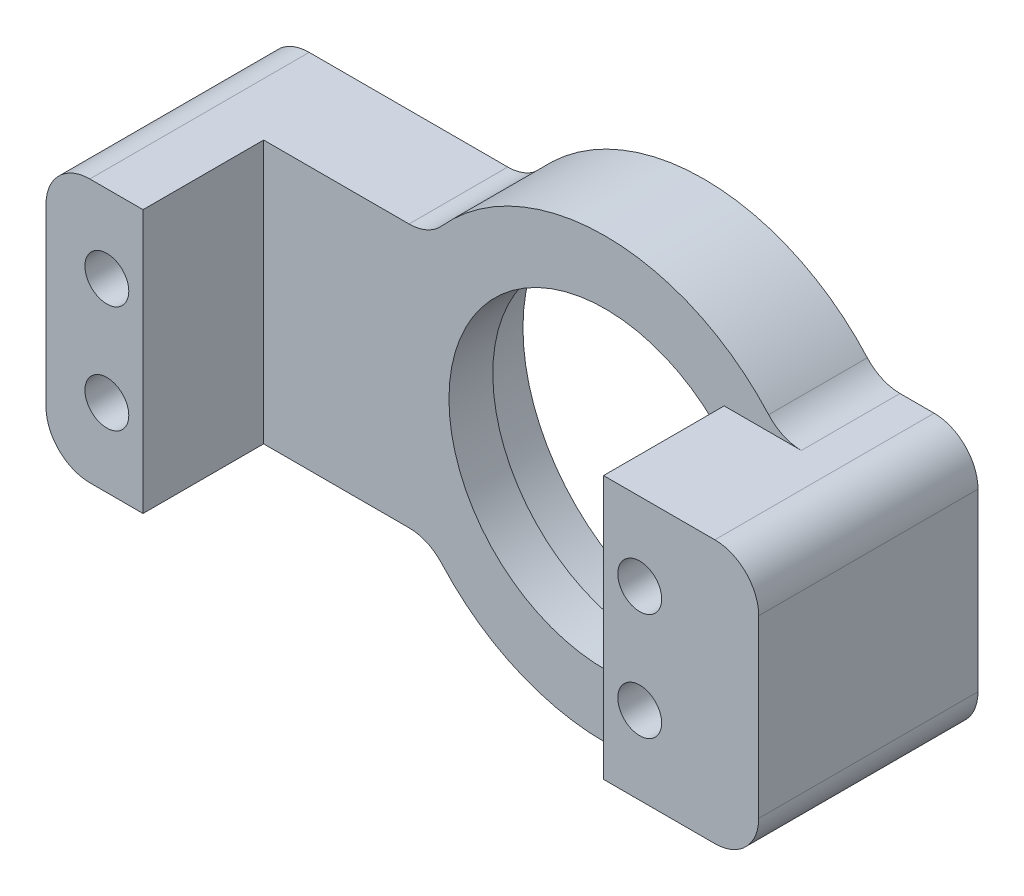
SolidWorks part; units mm, degrees
ref_plane "Front Plane" through (0, 0, 0) normal (0, 0, 1) x (1, 0, 0)
ref_plane "Top Plane" through (0, 0, 0) normal (0, 1, 0) x (1, 0, 0)
ref_plane "Right Plane" through (0, 0, 0) normal (1, 0, 0) x (0, 0, -1)
sketch "Sketch1" plane through (0, 0, 0) normal (0, 0, 1) x (1, 0, 0)
  line L0 (0, 113.0073) -> (17, 113.0073) construction
  line L1 (-40, 125.0073) -> (-16, 125.0073)
  line L2 (-40, 125.0073) -> (-40, 101.0073)
  line L3 (-40, 101.0073) -> (-16, 101.0073)
  line L4 (25, 125.0073) -> (25, 101.0073)
  line L6 (16, 125.0073) -> (25, 125.0073)
  line L8 (16, 101.0073) -> (25, 101.0073)
  arc A0 (16, 125.0073) -> (-16, 125.0073) centre (0, 113.0073) ccw
  circle A1 centre (0, 113.0073) radius 16.5
  arc A2 (-16, 101.0073) -> (16, 101.0073) centre (0, 113.0073) ccw
  dimension "D1" = 12
  dimension "D3" = 25
  dimension "D4" = 40
extrude "Boss-Extrude1" add sketch "Sketch1" along normal blind 5
sketch "Sketch2" plane through (0, 0, 5) normal (0, 0, 1) x (1, 0, 0)
  line L6 (-16, 125.0073) -> (-40, 125.0073)
  line L7 (-40, 125.0073) -> (-40, 101.0073)
  line L8 (-40, 101.0073) -> (-16, 101.0073)
  line L9 (16, 101.0073) -> (25, 101.0073)
  line L10 (25, 101.0073) -> (25, 125.0073)
  line L11 (25, 125.0073) -> (16, 125.0073)
  line L12 (-16, 125.0073) -> (-40, 125.0073)
  line L13 (-40, 125.0073) -> (-40, 101.0073)
  line L14 (-40, 101.0073) -> (-16, 101.0073)
  line L15 (16, 101.0073) -> (25, 101.0073)
  line L16 (25, 101.0073) -> (25, 125.0073)
  line L17 (25, 125.0073) -> (16, 125.0073)
  circle A0 centre (0, 113.0073) radius 14.25
  arc A2 (-16, 101.0073) -> (16, 101.0073) centre (0, 113.0073) ccw
  arc A3 (16, 125.0073) -> (-16, 125.0073) centre (0, 113.0073) ccw
  arc A4 (-16, 101.0073) -> (16, 101.0073) centre (0, 113.0073) ccw
  arc A5 (16, 125.0073) -> (-16, 125.0073) centre (0, 113.0073) ccw
  dimension "D1" = 0
extrude "Boss-Extrude2" add sketch "Sketch2" along normal blind 4
sketch "Sketch4" plane through (0, 0, 9) normal (0, 0, 1) x (1, 0, 0)
  line L0 (-40, 101.0073) -> (-16, 101.0073) construction
  line L1 (25, 101.0073) -> (10.85, 101.0073)
  line L2 (25, 101.0073) -> (25, 125.0073)
  line L3 (25, 125.0073) -> (10.85, 125.0073)
  line L4 (10.85, 101.0073) -> (10.85, 125.0073)
  line L5 (-40, 125.0073) -> (-31.15, 125.0073)
  line L6 (-40, 125.0073) -> (-40, 101.0073)
  line L7 (-40, 101.0073) -> (-31.15, 101.0073)
  line L8 (-31.15, 125.0073) -> (-31.15, 101.0073)
  line L11 (25, 125.0073) -> (16, 125.0073) construction
extrude "Boss-Extrude4" add sketch "Sketch4" along normal blind 11
fillet "Fillet1" radius 4 8 edges at (16, 125.0073, 4.5) (-16, 125.0073, 4.5) (-16, 101.0073, 4.5) (16, 101.0073, 4.5) (-40, 101.0073, 10) (-40, 125.0073, 10) (25, 125.0073, 10) (25, 101.0073, 10)
sketch "Sketch5" plane through (0, 0, 20) normal (0, 0, 1) x (1, 0, 0)
  circle A0 centre (-34.45, 108.1073) radius 2
  circle A1 centre (-34.45, 117.9073) radius 2
  circle A2 centre (14.15, 108.1073) radius 2
  circle A3 centre (14.15, 117.9073) radius 2
  point P12 (0, 0)
  point P13 (0, 0)
  point P14 (0, 0)
  point P15 (0, 0)
  point P16 (0, 0)
extrude "Cut-Extrude1" cut sketch "Sketch5" against normal blind 4
